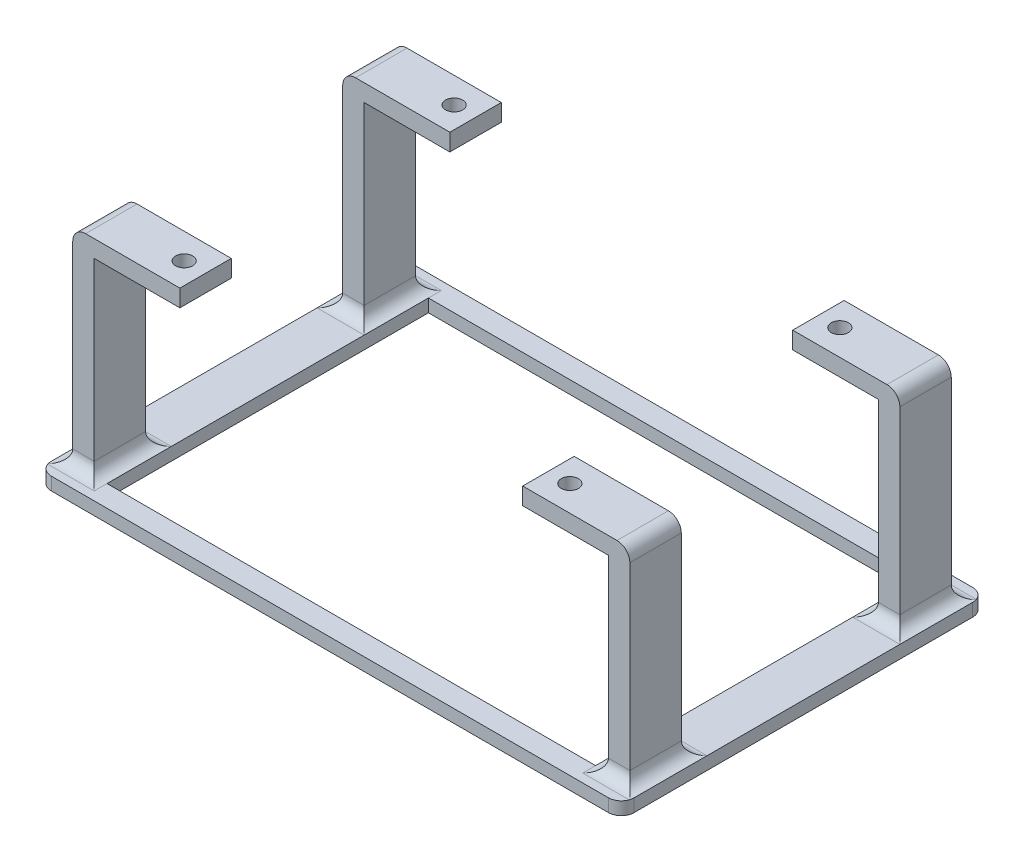
SolidWorks part; units mm, degrees
ref_plane "Front Plane" through (0, 0, 0) normal (0, 0, 1) x (1, 0, 0)
ref_plane "Top Plane" through (0, 0, 0) normal (0, 1, 0) x (1, 0, 0)
ref_plane "Right Plane" through (0, 0, 0) normal (1, 0, 0) x (0, 0, -1)
sketch "Sketch1" plane through (0, 0, 0) normal (0, 1, 0) x (1, 0, 0)
  line L1 (0, 0) -> (114, 0)
  line L2 (0, 0) -> (0, 75)
  line L3 (0, 75) -> (114, 75)
  line L4 (114, 0) -> (114, 75)
  line L9 (-11, 80) -> (125, 80)
  line L10 (-11, 80) -> (-11, -5)
  line L11 (-11, -5) -> (125, -5)
  line L12 (125, 80) -> (125, -5)
  dimension "D1" = 75
  dimension "D2" = 114
extrude "Boss-Extrude1" add sketch "Sketch1" along normal blind 3
sketch "Sketch2" plane through (0, 3, 0) normal (0, 1, 0) x (1, 0, 0)
  line L1 (-3, 75) -> (-3, 63)
  line L2 (-3, 63) -> (-8, 63)
  line L3 (-8, 63) -> (-8, 75)
  line L4 (-8, 75) -> (-3, 75)
  line L8 (-8, 0) -> (-3, 0)
  line L9 (-8, 12) -> (-8, 0)
  line L10 (-3, 12) -> (-8, 12)
  line L11 (-3, 0) -> (-3, 12)
  line L12 (117, 0) -> (117, 12)
  line L13 (117, 12) -> (122, 12)
  line L14 (122, 12) -> (122, 0)
  line L15 (122, 0) -> (117, 0)
  line L16 (122, 75) -> (117, 75)
  line L17 (122, 63) -> (122, 75)
  line L18 (117, 63) -> (122, 63)
  line L19 (117, 75) -> (117, 63)
extrude "Boss-Extrude2" add sketch "Sketch2" along normal blind 48
fillet "Fillet1" radius 3 8 edges at (-8, 51, -6) (-8, 51, -69) (122, 51, -69) (122, 51, -6) (125, 1.5, 5) (125, 1.5, -80) (-11, 1.5, -80) (-11, 1.5, 5)
sketch "Sketch3" plane through (0, 51, 0) normal (0, 1, 0) x (1, 0, 0)
  line L0 (117, 0) -> (97, 0)
  line L1 (97, 0) -> (97, 12)
  line L2 (97, 12) -> (117, 12)
  line L3 (117, 12) -> (117, 0)
  line L7 (-3, 12) -> (-3, 0)
  line L8 (17, 12) -> (-3, 12)
  line L9 (17, 0) -> (17, 12)
  line L10 (-3, 0) -> (17, 0)
  line L11 (117, 63) -> (117, 75)
  line L12 (97, 63) -> (117, 63)
  line L13 (97, 75) -> (97, 63)
  line L14 (117, 75) -> (97, 75)
  line L15 (-3, 75) -> (17, 75)
  line L16 (17, 75) -> (17, 63)
  line L17 (17, 63) -> (-3, 63)
  line L18 (-3, 63) -> (-3, 75)
  circle A0 centre (102, 6) radius 2
  circle A1 centre (12, 6) radius 2
  circle A2 centre (102, 69) radius 2
  circle A3 centre (12, 69) radius 2
extrude "Boss-Extrude3" add sketch "Sketch3" against normal blind 4
fillet "Fillet2" radius 3 16 edges at (-8, 3, -6) (-5.5, 3, 0) (-3, 3, -6) (-5.5, 3, -12) (-5.5, 3, -63) (-3, 3, -69) (-8, 3, -69) (-5.5, 3, -75) (117, 3, -6) (119.5, 3, 0) (122, 3, -6) (119.5, 3, -12) (119.5, 3, -63) (122, 3, -69) (119.5, 3, -75) (117, 3, -69)
